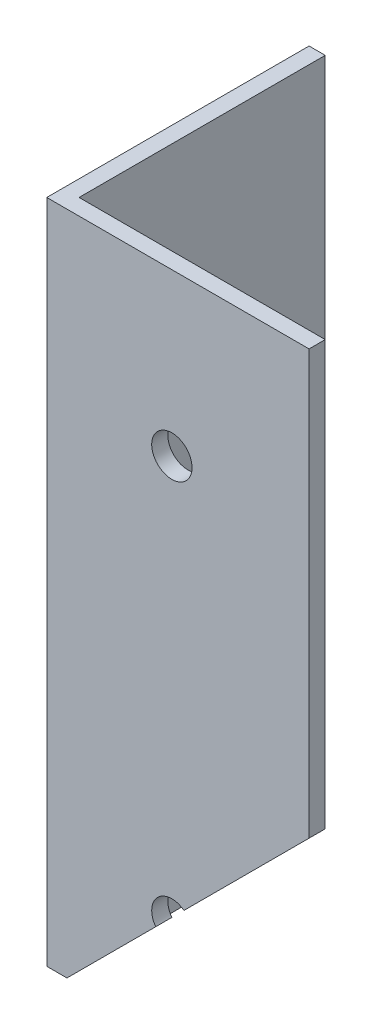
SolidWorks part; units mm, degrees
ref_plane "Спереди" through (0, 0, 0) normal (0, 0, 1) x (1, 0, 0)
ref_plane "Сверху" through (0, 0, 0) normal (0, 1, 0) x (1, 0, 0)
ref_plane "Справа" through (0, 0, 0) normal (1, 0, 0) x (0, 0, -1)
sketch "Эскиз1" plane through (0, 0, 0) normal (0, 1, 0) x (1, 0, 0)
  line L0 (0, 0) -> (65, 0)
  line L1 (0, 0) -> (0, 65)
extrude "Вытянуть-Тонкостенный1" add sketch "Эскиз1" along normal blind 165 thin thin type one direction wall 4
sketch "Эскиз2" plane through (0, 0, 0) normal (0, 0, 1) x (1, 0, 0)
  circle A0 centre (31, 225) radius 5
  circle A1 centre (31, 125) radius 5
  circle A2 centre (31, 25) radius 5
  dimension "D1" = 3
extrude "Вырез-Вытянуть1" cut sketch "Эскиз2" against normal blind 10
sketch "Эскиз3" plane through (0, 0, 0) normal (-1, 0, 0) x (0, 0, 1)
  circle A0 centre (-31, 225) radius 5
  circle A1 centre (-31, 125) radius 5
  circle A2 centre (-31, 25) radius 5
  dimension "D1" = 3
extrude "Вырез-Вытянуть2" cut sketch "Эскиз3" against normal blind 10
sketch "Эскиз4" plane through (0, 0, 0) normal (0, 0, 1) x (1, 0, 0)
  line L0 (5, 0) -> (65, 60)
  line L1 (65, 0) -> (0, 0) construction
  line L2 (65, 165) -> (65, 0) construction
  line L3 (65, 60) -> (65, 0)
  line L4 (65, 0) -> (5, 0)
extrude "Вырез-Вытянуть3" cut sketch "Эскиз4" against normal through all
